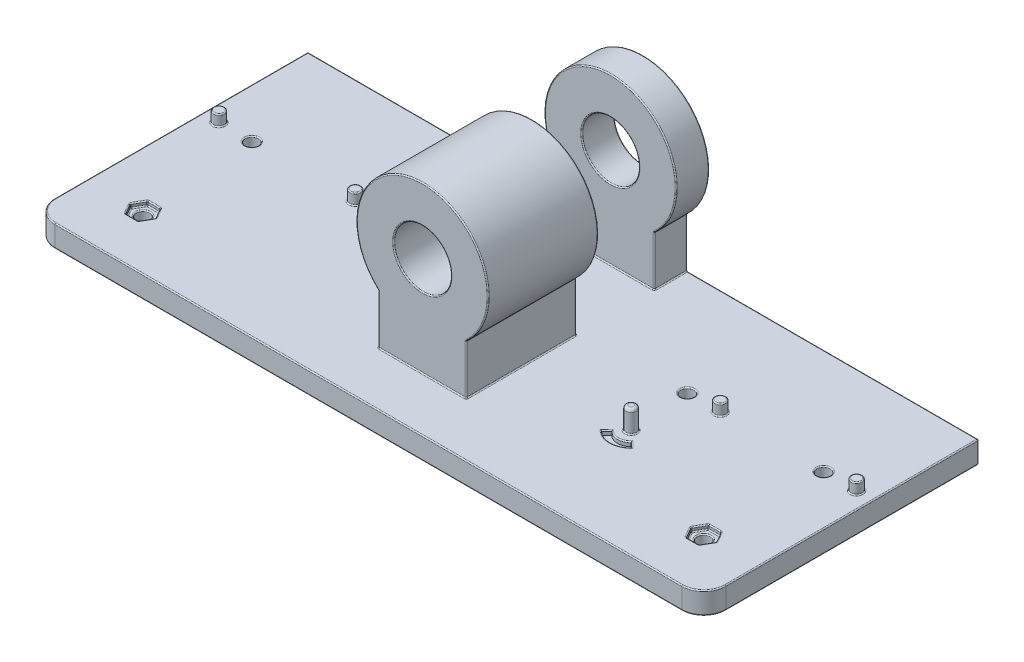
SolidWorks part; units mm, degrees
ref_plane "Front Plane" through (0, 0, 0) normal (0, 0, 1) x (1, 0, 0)
ref_plane "Top Plane" through (0, 0, 0) normal (0, 1, 0) x (1, 0, 0)
ref_plane "Right Plane" through (0, 0, 0) normal (1, 0, 0) x (0, 0, -1)
sketch "Sketch1" plane through (0, 0, 0) normal (0, 1, 0) x (1, 0, 0)
  line L0 (152.5, 125) -> (152.5, 0) construction
  line L1 (0, 0) -> (305, 0)
  line L2 (0, 0) -> (0, 125)
  line L3 (0, 125) -> (305, 125)
  line L4 (305, 0) -> (305, 125)
  line L5 (25, 100) -> (280, 100) construction
  line L6 (280, 25) -> (280, 100) construction
  line L7 (25, 25) -> (280, 25) construction
  line L8 (25, 25) -> (25, 100) construction
  line L9 (152.5, 62.5) -> (25, 62.5) construction
  line L10 (30.7735, 100) -> (27.8868, 105) construction
  line L11 (27.8868, 105) -> (22.1132, 105) construction
  line L12 (22.1132, 105) -> (19.2265, 100) construction
  line L13 (19.2265, 100) -> (22.1132, 95) construction
  line L14 (22.1132, 95) -> (27.8868, 95) construction
  line L15 (27.8868, 95) -> (30.7735, 100) construction
  line L16 (27.8868, 30) -> (30.7735, 25) construction
  line L17 (22.1132, 30) -> (27.8868, 30) construction
  line L18 (19.2265, 25) -> (22.1132, 30) construction
  line L19 (22.1132, 20) -> (19.2265, 25) construction
  line L20 (27.8868, 20) -> (22.1132, 20) construction
  line L21 (30.7735, 25) -> (27.8868, 20) construction
  line L22 (282.8868, 30) -> (277.1132, 30) construction
  line L23 (285.7735, 25) -> (282.8868, 30) construction
  line L24 (282.8868, 20) -> (285.7735, 25) construction
  line L25 (277.1132, 20) -> (282.8868, 20) construction
  line L26 (274.2265, 25) -> (277.1132, 20) construction
  line L27 (277.1132, 30) -> (274.2265, 25) construction
  line L28 (277.1132, 95) -> (274.2265, 100) construction
  line L29 (282.8868, 95) -> (277.1132, 95) construction
  line L30 (285.7735, 100) -> (282.8868, 95) construction
  line L31 (282.8868, 105) -> (285.7735, 100) construction
  line L32 (277.1132, 105) -> (282.8868, 105) construction
  line L33 (274.2265, 100) -> (277.1132, 105) construction
  line L34 (172.5, 75) -> (172.5, 125) construction
  line L35 (132.5, 0) -> (172.5, 0) construction
  line L36 (132.5, 0) -> (132.5, 125) construction
  line L37 (132.5, 125) -> (172.5, 125) construction
  line L38 (172.5, 0) -> (172.5, 125) construction
  line L39 (132.5, 75) -> (172.5, 75) construction
  line L40 (132.5, 75) -> (132.5, 25) construction
  line L41 (132.5, 25) -> (172.5, 25) construction
  line L42 (172.5, 75) -> (172.5, 25) construction
  line L51 (0, 84.5) -> (15, 69.5) construction
  line L52 (132.5, 75) -> (117.5, 60) construction
  line L53 (117.5, 60) -> (117.5, 85) construction
  line L54 (0, 125) -> (108, 125) construction
  line L55 (0, 125) -> (0, 84.5) construction
  line L56 (0, 84.5) -> (108, 84.5) construction
  line L57 (108, 125) -> (108, 84.5) construction
  line L58 (15, 69.5) -> (15, 84.5) construction
  line L59 (30, 84.5) -> (0, 84.5) construction
  line L60 (30, 84.5) -> (30, 69.5) construction
  line L61 (30, 69.5) -> (0, 69.5) construction
  line L62 (0, 84.5) -> (0, 69.5) construction
  line L63 (92, 84.5) -> (92, 69.5) construction
  line L64 (62, 0) -> (62, 125) construction
  circle A1 centre (25, 100) radius 5 construction
  circle A3 centre (280, 25) radius 3
  circle A4 centre (25, 25) radius 3
  circle A8 centre (117.5, 60) radius 3
  circle A9 centre (117.5, 85) radius 3
  circle A10 centre (7.5, 77) radius 3 construction
  circle A11 centre (22.5, 77) radius 3
  circle A12 centre (69.5, 77) radius 3 construction
  circle A13 centre (84.5, 77) radius 3
  circle A14 centre (220.5, 77) radius 3
  circle A15 centre (235.5, 77) radius 3 construction
  circle A16 centre (282.5, 77) radius 3
  circle A17 centre (297.5, 77) radius 3 construction
  dimension "D3" = 6
  dimension "D1" = 305
  dimension "D2" = 125
  dimension "D5" = 10
  dimension "D6" = 40
  dimension "D8" = 50
  dimension "D12" = 15
  dimension "D7" = 40.5
  dimension "D9" = 108
  dimension "D10" = 15
  dimension "D11" = 30
  dimension "D15" = 62
  dimension "D16" = 15
  dimension "D17" = 25
  dimension "D4" = 25
  dimension "D13" = 2
  dimension "D14" = 2
extrude "Boss-Extrude1" add sketch "Sketch1" along normal blind 10
sketch "Sketch7" plane through (0, 10, 0) normal (0, 1, 0) x (1, 0, 0)
  line L0 (0, 0) -> (305, 0) construction
  line L1 (132.5, 24.5) -> (172.5, 24.5)
  line L2 (132.5, 24.5) -> (132.5, 74.5)
  line L3 (132.5, 74.5) -> (172.5, 74.5)
  line L4 (172.5, 24.5) -> (172.5, 74.5)
  line L5 (152.5, 0) -> (152.5, 125) construction
  line L6 (305, 125) -> (0, 125) construction
  line L18 (132.5, 110) -> (172.5, 110)
  line L19 (132.5, 110) -> (132.5, 125)
  line L20 (132.5, 125) -> (172.5, 125)
  line L21 (172.5, 110) -> (172.5, 125)
  point P11 (152.5, 74.5)
  point P20 (152.5, 110)
  dimension "D1" = 40
  dimension "D2" = 50
  dimension "D4" = 15
  dimension "D3" = 35.5
extrude "Boss-Extrude2" add sketch "Sketch7" along normal blind 22.6393
sketch "Sketch11" plane through (0, 0, -24.5) normal (0, 0, 1) x (1, 0, 0)
  circle A0 centre (152.5, 55) radius 30
  circle A1 centre (152.5, 55) radius 13
  dimension "D1" = 60
  dimension "D2" = 26
extrude "Boss-Extrude3" add sketch "Sketch11" against normal up to surface (100.5 mm away) up to face at (152.5, 13.1598, -125)
ref_plane "Plane1" through (0, 0, -62.5) normal (0, 0, 1) x (1, 0, 0)
sketch "Sketch12" plane through (305, 0, 0) normal (1, 0, 0) x (0, 0, -1)
  line L0 (125, 85) -> (24.5, 85) construction
  line L1 (74.5, 10) -> (110, 10)
  line L2 (74.5, 10) -> (74.5, 85)
  line L3 (74.5, 85) -> (110, 85)
  line L4 (110, 10) -> (110, 85)
  line L6 (110, 32.6393) -> (110, 10) construction
extrude "Cut-Extrude2" cut sketch "Sketch12" against normal through all
sketch "Sketch13" plane through (0, 10, 0) normal (0, 1, 0) x (1, 0, 0)
  line L0 (222.5, 49.5) -> (172.5, 49.5) construction
  line L1 (172.5, 24.5) -> (172.5, 74.5) construction
  circle A1 centre (222.5, 49.5) radius 2.4
  dimension "D1" = 4.8
  dimension "D2" = 50
extrude "Boss-Extrude4" add sketch "Sketch13" along normal blind 10
sketch "Sketch6" plane through (0, 10, 0) normal (0, 1, 0) x (1, 0, 0)
  line L0 (152.5, 125) -> (152.5, 0) construction
  line L7 (215.7825, 42.7825) -> (218.0806, 45.0806)
  line L8 (0, 0) -> (305, 0) construction
  line L9 (152.5, 62.5) -> (0, 62.5) construction
  line L10 (0, 125) -> (0, 0) construction
  line L29 (27.8868, 30) -> (30.7735, 25)
  line L30 (274.2265, 25) -> (277.1132, 20)
  line L31 (277.1132, 20) -> (282.8868, 20)
  line L32 (282.8868, 20) -> (285.7735, 25)
  line L33 (285.7735, 25) -> (282.8868, 30)
  line L34 (282.8868, 30) -> (277.1132, 30)
  line L35 (277.1132, 30) -> (274.2265, 25)
  line L36 (22.1132, 30) -> (27.8868, 30)
  line L37 (19.2265, 25) -> (22.1132, 30)
  line L38 (22.1132, 20) -> (19.2265, 25)
  line L39 (27.8868, 20) -> (22.1132, 20)
  line L40 (30.7735, 25) -> (27.8868, 20)
  line L41 (231.3388, 40.6612) -> (213.6612, 58.3388) construction
  line L42 (213.6612, 40.6612) -> (231.3388, 58.3388) construction
  line L43 (222.5, 49.5) -> (222.5, 37) construction
  line L44 (213.6612, 40.6612) -> (222.5, 37) construction
  line L45 (222.5, 37) -> (231.3388, 40.6612) construction
  line L46 (229.2175, 42.7825) -> (226.9194, 45.0806)
  circle A0 centre (280, 25) radius 5 construction
  circle A1 centre (222.5, 49.5) radius 12.5 construction
  circle A2 centre (222.5, 49.5) radius 9.5 construction
  circle A3 centre (222.5, 49.5) radius 6.25 construction
  arc A4 (218.0806, 45.0806) -> (226.9194, 45.0806) centre (222.5, 49.5) ccw
  arc A5 (215.7825, 42.7825) -> (229.2175, 42.7825) centre (222.5, 49.5) ccw
  point P34 (0, 0)
  dimension "D2" = 25
  dimension "D4" = 12.5
  dimension "D1" = 10
  dimension "D3" = 3
extrude "Cut-Extrude1" cut sketch "Sketch6" against normal blind 2
fillet "Fillet1" radius 1.3 1 edges at (222.5, 20, -47.1)
sketch "Sketch15" plane through (0, 10, 0) normal (0, 1, 0) x (1, 0, 0)
  line L0 (69.5, 77) -> (7.5, 77) construction
  line L1 (38.5, 77) -> (38.5, 84.5) construction
  line L2 (0, 84.5) -> (108, 84.5) construction
  line L3 (152.5, 125) -> (152.5, 0) construction
  circle A1 centre (69.5, 77) radius 2.5
  circle A2 centre (7.5, 77) radius 2.5
  circle A3 centre (7.5, 77) radius 2.5
  circle A4 centre (235.5, 77) radius 2.5
  circle A5 centre (297.5, 77) radius 2.5
  dimension "D1" = 0.5
extrude "Boss-Extrude5" add sketch "Sketch15" along normal blind 5
chamfer "Chamfer1" distance 3.3 angle 45 6 edges at (282.5, 0, -74) (220.5, 0, -74) (84.5, 0, -80) (22.5, 0, -80) (117.5, 0, -57) (117.5, 0, -82)
fillet "Fillet2" radius 0.5 97 edges at (25, 0, -28) (19.2265, 9, -25) (22.1132, 9, -20) (27.8868, 9, -30) (22.1132, 9, -30) (27.8868, 9, -20) (30.7735, 9, -25) (29.3301, 8, -27.5) (29.3301, 8, -22.5) (25, 8, -20) (20.6699, 8, -22.5) (20.6699, 8, -27.5) (25, 8, -30) (25, 8, -28) (280, 0, -22) (277.1132, 9, -30) (274.2265, 9, -25) (285.7735, 9, -25) (282.8868, 9, -30) (277.1132, 9, -20) (282.8868, 9, -20) (280, 8, -30) (284.3301, 8, -27.5) (284.3301, 8, -22.5) (280, 8, -20) (275.6699, 8, -22.5) (275.6699, 8, -27.5) (280, 8, -22) (235.5, 15, -74.5) (297.5, 15, -79.5) (69.5, 15, -79.5) (7.5, 15, -74.5) (117.5, 10, -57) (280, 10, -20) (284.3301, 10, -22.5) (284.3301, 10, -27.5) (280, 10, -30) (275.6699, 10, -27.5) (275.6699, 10, -22.5) (20.6699, 10, -22.5) (25, 10, -20) (29.3301, 10, -22.5) (29.3301, 10, -27.5) (25, 10, -30) (20.6699, 10, -27.5) (117.5, 10, -82) (305, 10, -62.5) (152.5, 10, 0) (0, 10, -62.5) (22.5, 10, -80) (84.5, 10, -80) (220.5, 10, -74) (282.5, 10, -74) (222.5, 10, -51.9) (7.5, 10, -79.5) (69.5, 10, -79.5) (235.5, 10, -79.5) (297.5, 10, -79.5) (165.5, 55, -24.5) (152.5, 10, -24.5) (152.5, 85, -24.5) (132.5, 32.6393, -49.5) (132.5, 21.3197, -24.5) (132.5, 10, -49.5) (165.5, 55, -74.5) (152.5, 10, -74.5) (152.5, 85, -74.5) (132.5, 21.3197, -74.5) (172.5, 21.3197, -24.5) (172.5, 32.6393, -49.5) (172.5, 21.3197, -74.5) (172.5, 10, -49.5) (172.5, 32.6393, -117.5) (172.5, 10, -117.5) (132.5, 32.6393, -117.5) (132.5, 10, -117.5) (165.5, 55, -125) (66.25, 10, -125) (0, 5, -125) (152.5, 0, -125) (305, 5, -125) (238.75, 10, -125) (172.5, 21.3197, -125) (152.5, 85, -125) (132.5, 21.3197, -125) (139.5, 55, -110) (152.5, 10, -110) (132.5, 21.3197, -110) (152.5, 85, -110) (172.5, 21.3197, -110) (305, 0, -62.5) (152.5, 0, 0) (0, 0, -62.5) (222.5, 10, -43.25) (216.9315, 10, -43.9315) (222.5, 10, -40) (228.0685, 10, -43.9315)
fillet "Fillet3" radius 10 6 edges at (0.1464, 0.1464, -0.1464) (0.1464, 9.8536, -0.1464) (304.8536, 0.1464, -0.1464) (304.8536, 9.8536, -0.1464) (305, 5, 0) (0, 5, 0)
equation "\"joint_width\"=4"
equation "\"short_base_length\"=12.5"
equation "\"D2@Sketch1\"=\"short_base_length\""
equation "\"outer_diam_main_joint\"=6"
equation "\"D1@Sketch11\"=\"outer_diam_main_joint\""
equation "\"D1@Sketch7\"=\"outer_diam_main_joint\"-2"
equation "\"D1@Boss-Extrude2\"=(\"outer_diam_main_joint\"/2)+1.5cm-sqr((\"outer_diam_main_joint\"/2)^2-((\"outer_diam_main_joint\"-2)/2)^2)"
equation "\"D6@Sketch1\"=\"outer_diam_main_joint\"-2"
equation "\"pulleyside\"=1.5"
